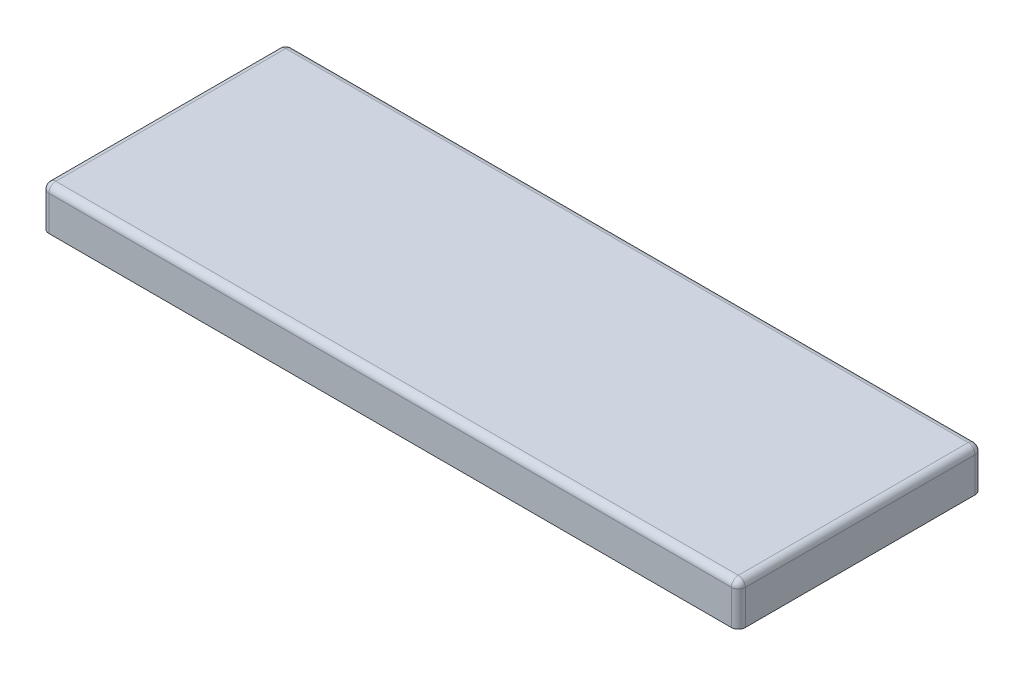
SolidWorks part; units mm, degrees
material "ABS"
ref_plane "前视基准面" through (0, 0, 0) normal (0, 0, 1) x (1, 0, 0)
ref_plane "上视基准面" through (0, 0, 0) normal (0, 1, 0) x (1, 0, 0)
ref_plane "右视基准面" through (0, 0, 0) normal (1, 0, 0) x (0, 0, -1)
ref_plane "BoxInnerTop" through (0, 0, 0) normal (0, 1, 0) x (1, 0, 0)
ref_plane "ConnectFace" through (0, -10, 0) normal (0, 1, 0) x (1, 0, 0)
sketch "SketchRec" plane through (0, 0, 0) normal (0, 1, 0) x (1, 0, 0)
  line L1 (-100, -35) -> (100, -35)
  line L2 (-100, -35) -> (-100, 35)
  line L3 (-100, 35) -> (100, 35)
  line L4 (100, -35) -> (100, 35)
  line L5 (-100, -35) -> (100, 35) construction
  line L6 (-100, 35) -> (100, -35) construction
  point P0 (0, 0)
  dimension "L" = 200
  dimension "KD" = 70
extrude "RectangleBox" add sketch "SketchRec" along normal blind 2 and the other way blind 10
fillet "RectangleR" radius 2 8 edges at (-100, -4, 35) (-100, -4, -35) (100, -4, -35) (100, -4, 35) (100, 2, 0) (0, 2, -35) (-100, 2, 0) (0, 2, 35)
shell "RectangleC" thickness 2 removed face at (0, -10, 0)
sketch "SketchCircle" [suppressed] plane through (0, 0, 0) normal (0, 1, 0) x (1, 0, 0)
  circle A0 centre (0, 0) radius 80
  dimension "D1" = 160
extrude "CircleBox" [suppressed] add sketch "SketchCircle" along normal blind 2 and the other way blind 10 contours A0
fillet "CircleR" [suppressed] radius 2
shell "CircleC" [suppressed] thickness 2
equation "\"H\"= 10"
equation "\"Tn\"= 2"
equation "\"D1@RectangleBox\"=\"Tn\""
equation "\"D2@RectangleBox\"=\"H\""
equation "\"D1@CircleBox\"=\"Tn\""
equation "\"D2@CircleBox\"=\"H\""
equation "\"DisCt@ConnectFace\"=\"H\""
